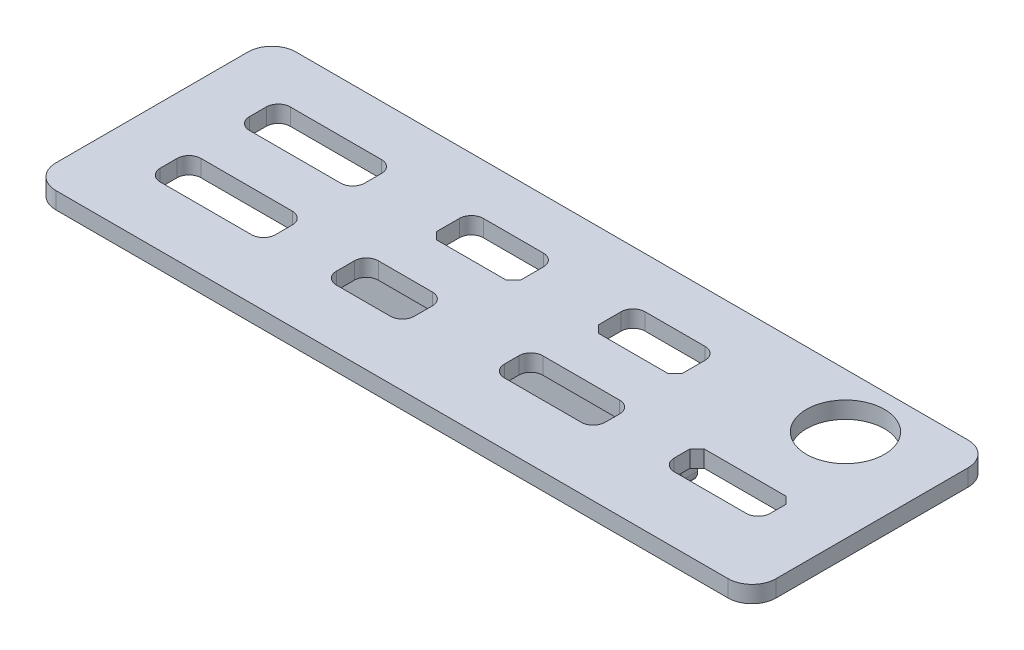
SolidWorks part; units mm, degrees
ref_plane "前视基准面" through (0, 0, 0) normal (0, 0, 1) x (1, 0, 0)
ref_plane "上视基准面" through (0, 0, 0) normal (0, 1, 0) x (1, 0, 0)
ref_plane "右视基准面" through (0, 0, 0) normal (1, 0, 0) x (0, 0, -1)
sketch "草图1" plane through (0, 0, 0) normal (0, 1, 0) x (1, 0, 0)
  line L1 (-30, 10) -> (30, 10)
  line L2 (-30, 10) -> (-30, -10)
  line L3 (-30, -10) -> (30, -10)
  line L4 (30, 10) -> (30, -10)
  line L5 (-30, 10) -> (30, -10) construction
  line L6 (-30, -10) -> (30, 10) construction
  point P0 (0, 0)
  dimension "D1" = 60
  dimension "D2" = 20
extrude "凸台-拉伸1" add sketch "草图1" along normal blind 1.4
fillet "圆角1" radius 2 4 edges at (30, 0.7, 10) (30, 0.7, -10) (-30, 0.7, 10) (-30, 0.7, -10)
sketch "草图4" plane through (0, 1.4, 0) normal (0, 1, 0) x (1, 0, 0)
  line L0 (-30, 8) -> (-30, -8) construction
  line L1 (-25.2717, 5.8) -> (-15.6717, 5.8)
  line L2 (-25.2717, 5.8) -> (-25.2717, 2.4)
  line L3 (-25.2717, 2.4) -> (-15.6717, 2.4)
  line L4 (-15.6717, 5.8) -> (-15.6717, 2.4)
  line L5 (-9.1829, 5.8) -> (-2.1829, 5.8)
  line L6 (-9.1829, 5.8) -> (-9.1829, 2.3)
  line L7 (-9.1829, 2.3) -> (-2.1829, 2.3)
  line L8 (-2.1829, 5.8) -> (-2.1829, 2.3)
  line L9 (4.2885, 5.8) -> (11.2885, 5.8)
  line L10 (4.2885, 5.8) -> (4.2885, 2.3)
  line L11 (4.2885, 2.3) -> (11.2885, 2.3)
  line L12 (11.2885, 5.8) -> (11.2885, 2.3)
  line L13 (17.05, -1.6348) -> (25.05, -1.6348)
  line L14 (17.05, -1.6348) -> (17.05, -4.5348)
  line L15 (17.05, -4.5348) -> (25.05, -4.5348)
  line L16 (25.05, -1.6348) -> (25.05, -4.5348)
  line L17 (3.2, -1.6348) -> (11.6, -1.6348)
  line L18 (3.2, -1.6348) -> (3.2, -4.8348)
  line L19 (3.2, -4.8348) -> (11.6, -4.8348)
  line L20 (11.6, -1.6348) -> (11.6, -4.8348)
  line L21 (-10.5, -1.6348) -> (-4, -1.6348)
  line L22 (-10.5, -1.6348) -> (-10.5, -5.1348)
  line L23 (-10.5, -5.1348) -> (-4, -5.1348)
  line L24 (-4, -1.6348) -> (-4, -5.1348)
  line L25 (-25.2717, -1.6348) -> (-15.6717, -1.6348)
  line L26 (-25.2717, -1.6348) -> (-25.2717, -5.0348)
  line L27 (-25.2717, -5.0348) -> (-15.6717, -5.0348)
  line L28 (-15.6717, -1.6348) -> (-15.6717, -5.0348)
  line L29 (28, 10) -> (-28, 10) construction
  line L30 (-28, -10) -> (28, -10) construction
  line L31 (30, -8) -> (30, 8) construction
  circle A0 centre (22.2985, 5.4832) radius 3.25
  dimension "D21" = 6.5
  dimension "D1" = 3.5
  dimension "D2" = 6.5
  dimension "D3" = 8.4
  dimension "D4" = 3.2
  dimension "D5" = 9.6
  dimension "D6" = 3.4
  dimension "D7" = 7
  dimension "D8" = 8
  dimension "D9" = 2.9
  dimension "D10" = 4.7283
  dimension "D11" = 7.6
  dimension "D12" = 4.9652
  dimension "D13" = 19.5
  dimension "D14" = 33.2
  dimension "D15" = 4.95
  dimension "D16" = 7
  dimension "D17" = 20.8171
  dimension "D18" = 34.2885
  dimension "D19" = 7.7015
  dimension "D20" = 4.5168
  dimension "D22" = 3.5
extrude "切除-拉伸1" cut sketch "草图4" against normal up to next
fillet "圆角2" radius 1 22 edges at (-25.2717, 0.7, -2.4) (-25.2717, 0.7, -5.8) (-15.6717, 0.7, -2.4) (-15.6717, 0.7, -5.8) (-2.1829, 0.7, -5.8) (-9.1829, 0.7, -5.8) (4.2885, 0.7, -5.8) (11.2885, 0.7, -5.8) (25.05, 0.7, 4.5348) (17.05, 0.7, 4.5348) (11.6, 0.7, 4.8348) (11.6, 0.7, 1.6348) (3.2, 0.7, 1.6348) (3.2, 0.7, 4.8348) (-4, 0.7, 5.1348) (-4, 0.7, 1.6348) (-10.5, 0.7, 1.6348) (-10.5, 0.7, 5.1348) (-15.6717, 0.7, 5.0348) (-15.6717, 0.7, 1.6348) (-25.2717, 0.7, 1.6348) (-25.2717, 0.7, 5.0348)
chamfer "倒角1" distance 0.6 angle 45 6 edges at (-9.1829, 0.7, -2.3) (-2.1829, 0.7, -2.3) (4.2885, 0.7, -2.3) (11.2885, 0.7, -2.3) (17.05, 0.7, 1.6348) (25.05, 0.7, 1.6348)
sketch "草图5" plane through (0, 0, 0) normal (0, -1, 0) x (1, 0, 0)
  line L0 (-30, -8) -> (-30, 8) construction
  line L1 (-13.9089, -4.8832) -> (-12.4089, -4.8832)
  line L2 (-13.9089, -4.8832) -> (-13.9089, 3.1168)
  line L3 (-13.9089, 3.1168) -> (-12.4089, 3.1168)
  line L4 (-12.4089, -4.8832) -> (-12.4089, 3.1168)
  line L5 (13.0911, -4.8832) -> (14.5911, -4.8832)
  line L6 (13.0911, -4.8832) -> (13.0911, 3.1168)
  line L7 (13.0911, 3.1168) -> (14.5911, 3.1168)
  line L8 (14.5911, -4.8832) -> (14.5911, 3.1168)
  line L9 (28, -10) -> (-28, -10) construction
  line L10 (30, 8) -> (30, -8) construction
  dimension "D1" = 1.5
  dimension "D2" = 8
  dimension "D3" = 1.5
  dimension "D4" = 8
  dimension "D5" = 16.0911
  dimension "D6" = 5.1168
  dimension "D7" = 5.1168
  dimension "D8" = 15.4089
extrude "凸台-拉伸2" add sketch "草图5" along normal blind 0.95
sketch "草图6" plane through (0, 0, 0) normal (0, -1, 0) x (1, 0, 0)
  line L0 (-13.9089, 3.1168) -> (-13.9089, -4.8832) construction
  line L1 (-13.9089, 0.5168) -> (14.5911, 0.5168)
  line L2 (-13.9089, 0.5168) -> (-13.9089, -0.8832)
  line L3 (-13.9089, -0.8832) -> (14.5911, -0.8832)
  line L4 (14.5911, 0.5168) -> (14.5911, -0.8832)
extrude "凸台-拉伸3" add sketch "草图6" along normal blind 4
fillet "圆角3" radius 1 2 edges at (14.5911, -4, -0.1832) (-13.9089, -4, -0.1832)
chamfer "倒角2" distance 1 angle 45 4 edges at (13.8411, -0.95, -4.8832) (-13.1589, -0.95, -4.8832) (13.8411, -0.95, 3.1168) (-13.1589, -0.95, 3.1168)
